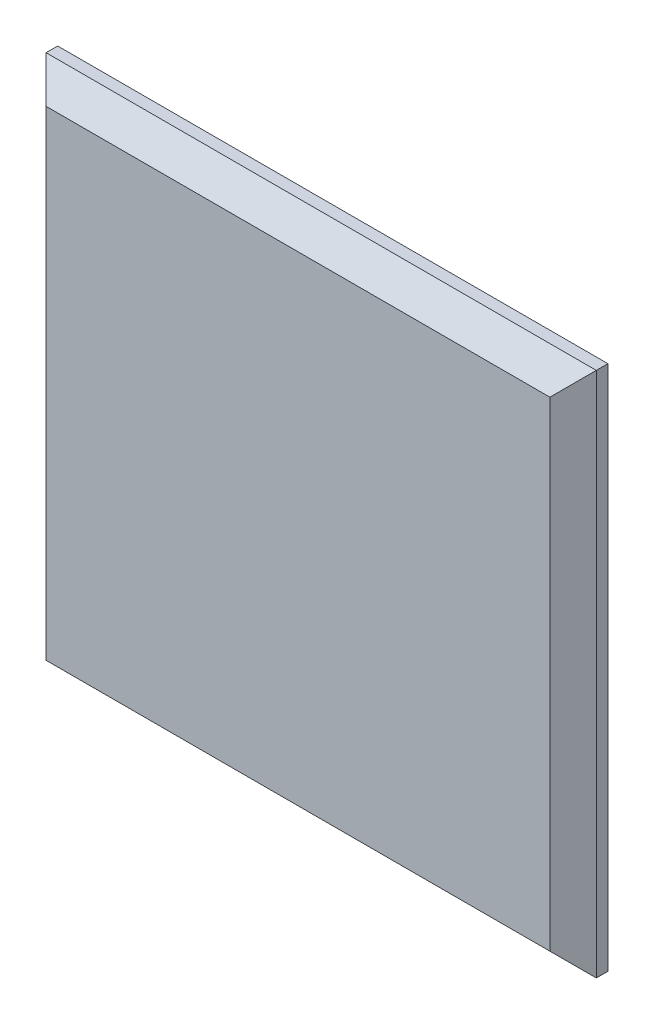
SolidWorks part; units mm, degrees
ref_plane "Front Plane" through (0, 0, 0) normal (0, 0, 1) x (1, 0, 0)
ref_plane "Top Plane" through (0, 0, 0) normal (0, 1, 0) x (1, 0, 0)
ref_plane "Right Plane" through (0, 0, 0) normal (1, 0, 0) x (0, 0, -1)
sketch "Sketch1" plane through (0, 0, 0) normal (0, 0, 1) x (1, 0, 0)
  line L0 (-8, 6.5) -> (-8, 5)
  line L1 (-137.2, 73) -> (-137.2, 85)
  line L2 (-8, 129.5) -> (-8, 131)
  line L3 (-132.7, 6.5) -> (-132.7, 5)
  line L4 (-135.7, 9.5) -> (-137.2, 9.5)
  line L5 (-132.7, 129.5) -> (-132.7, 133)
  line L6 (-135.7, 126.5) -> (-137.2, 126.5)
  line L7 (0, 136) -> (-142.2, 136)
  line L8 (0, 0) -> (0, 136)
  line L9 (-142.2, 0) -> (0, 0)
  line L12 (-142.2, 136) -> (-142.2, 0)
  line L13 (-137.2, 5) -> (-137.2, 131)
  line L14 (-137.2, 5) -> (-5, 5)
  line L15 (-5, 5) -> (-5, 131)
  line L16 (-5, 131) -> (-137.2, 131)
  circle A0 centre (-5, 129.5) radius 3
  circle A1 centre (-5, 6.5) radius 3
  circle A2 centre (-135.7, 129.5) radius 3
  circle A3 centre (-135.7, 6.5) radius 3
  dimension "D2" = 6
  dimension "D3" = 1.5
  dimension "D4" = 6
  dimension "D5" = 6
  dimension "D6" = 1.5
  dimension "D1" = 6
  dimension "D7" = 1.5
  dimension "D8" = 1.5
  dimension "D9" = 1.5
  dimension "D10" = 1.5
extrude "Boss-Extrude1" add sketch "Sketch1" along normal blind 6 contours L16 A0 L15 | A0 L16 L2 | L15 A0 L16 | L7 L12 L9 L8 A3 L13 L1 A2 L16 A0 L15 A1 L14 | L16 A2 L13 | A2 L16 L13 | A2 L5 L16 | A2 L13 L6 | L13 A3 L14 | A3 L13 L14 | A3 L14 L3 | A3 L4 L13 | L14 A1 L15 | L15 A1 L14 | A1 L0 L14 region at (-7.8809, 5.3698, 0) region at (-6.3354, 7.014, 0) region at (-4.1014, 6.1541, 0) region at (-132.8191, 5.3698, 0) region at (-6.3354, 128.986, 0) region at (-4.1014, 129.8459, 0) region at (-135.1229, 7.0771, 0) region at (-137.7653, 4.4347, 0) region at (-7.8809, 130.6302, 0) region at (-136.8302, 9.3809, 0) region at (-132.8191, 130.6302, 0) region at (-135.1229, 128.9229, 0) region at (-135.151, 131.0792, 0) region at (-136.8302, 126.6191, 0) region at (-1.9677, 68, 0)
sketch "Sketch2" plane through (0, 0, 6) normal (0, 0, 1) x (1, 0, 0)
  line L4 (-142.2, 0) -> (0, 0) construction
  line L5 (0, 0) -> (0, 136) construction
  line L6 (0, 136) -> (-142.2, 136) construction
  line L7 (-142.2, 136) -> (-142.2, 0) construction
  line L8 (-142.2, 0) -> (0, 0)
  line L9 (0, 0) -> (0, 136)
  line L10 (0, 136) -> (-142.2, 136)
  line L11 (-142.2, 136) -> (-142.2, 0)
extrude "Boss-Extrude2" add sketch "Sketch2" along normal blind 3
chamfer "Chamfer1" distance 6 angle 45 4 edges at (-71.1, 136, 9) (0, 68, 9) (-71.1, 0, 9) (-142.2, 68, 9)
chamfer "Chamfer2" distance 4 angle 45 4 edges at (-70.35, 131, 6) (-5, 68, 6) (-70.35, 5, 6) (-137.2, 68, 6)
sketch "Sketch3" plane through (0, 0, 0) normal (0, 0, -1) x (-1, 0, 0)
  circle A4 centre (135.7, 129.5) radius 1.55
  circle A5 centre (135.7, 6.5) radius 1.55
  circle A6 centre (5, 6.5) radius 1.55
  circle A7 centre (5, 129.5) radius 1.55
  dimension "D1" = 3.1
  dimension "D2" = 3.1
  dimension "D3" = 3.1
  dimension "D4" = 3.1
extrude "Cut-Extrude1" cut sketch "Sketch3" against normal blind 2.3
